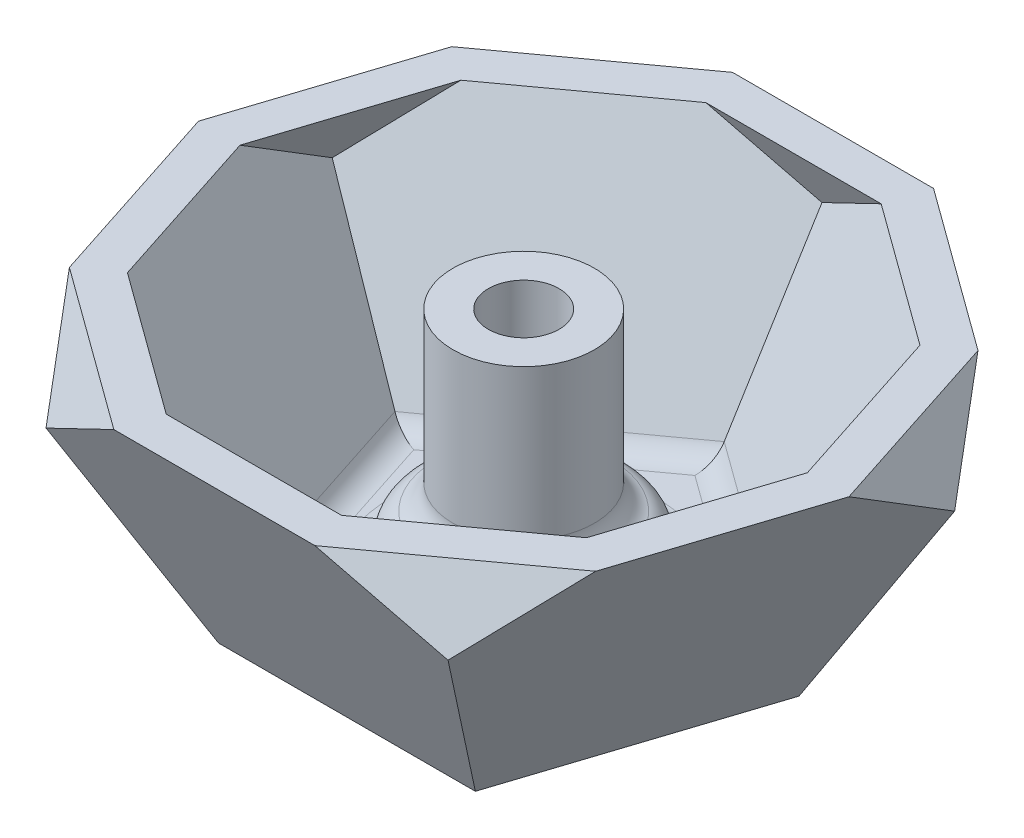
SolidWorks part; units mm, degrees
ref_plane "Front Plane" through (0, 0, 0) normal (0, 0, 1) x (1, 0, 0)
ref_plane "Top Plane" through (0, 0, 0) normal (0, 1, 0) x (1, 0, 0)
ref_plane "Right Plane" through (0, 0, 0) normal (1, 0, 0) x (0, 0, -1)
sketch "Sketch1" plane through (0, 0, 0) normal (0, 1, 0) x (1, 0, 0)
  line L1 (0, 12.3607) -> (-11.7557, 3.8197)
  line L2 (-11.7557, 3.8197) -> (-7.2654, -10)
  line L3 (-7.2654, -10) -> (7.2654, -10)
  line L4 (7.2654, -10) -> (11.7557, 3.8197)
  line L5 (11.7557, 3.8197) -> (0, 12.3607)
  circle A0 centre (0, 0) radius 10 construction
  dimension "D1" = 20
extrude "Boss-Extrude1" add sketch "Sketch1" along normal blind 30 draft 26.565 draft outward yes
sketch "Sketch3" plane through (0, 30, 0) normal (0, 1, 0) x (1, 0, 0)
  line L0 (0, 0) -> (14.6946, 20.2254) construction
  line L1 (7.2654, 10) -> (-7.2654, 10)
  line L2 (-7.2654, 10) -> (-11.7557, -3.8197)
  line L3 (-11.7557, -3.8197) -> (0, -12.3607)
  line L4 (0, -12.3607) -> (11.7557, -3.8197)
  line L5 (11.7557, -3.8197) -> (7.2654, 10)
  line L6 (29.3893, 9.5492) -> (0, 30.9017) construction
  circle A0 centre (0, 0) radius 10 construction
  dimension "D1" = 20
extrude "Cut-Extrude1" cut sketch "Sketch3" against normal blind 30 draft 26.565 flip side to cut
sketch "Sketch4" plane through (0, 0, 0) normal (1, 0, 0) x (0, 0, -1)
  line L0 (-3.8197, 30) -> (-3.8197, 0) construction
  line L1 (-10, 0) -> (3.8197, 0) construction
  point P5 (-3.8197, 15)
ref_plane "Plane1" through (0, 15, 0) normal (0, 1, 0) x (1, 0, 0)
sketch "Sketch5" plane through (0, 15, 0) normal (0, 1, 0) x (1, 0, 0)
  circle A0 centre (0, 0) radius 19.3475
extrude "Cut-Extrude2" cut sketch "Sketch5" along normal blind 25
shell "Shell1" thickness 2 removed face at (0, 15, 0)
sketch "Sketch6" plane through (0, 2, 0) normal (0, 1, 0) x (1, 0, 0)
  circle A0 centre (0, 0) radius 4
  circle A1 centre (0, 0) radius 2
  dimension "D1" = 8
  dimension "D2" = 4
extrude "Boss-Extrude2" add sketch "Sketch6" along direction (0, 1, 0) on the side of the normal up to surface (13 mm away) up to face at (0, 15, 0)
sketch "Sketch10" plane through (0, 2, 0) normal (0, 1, 0) x (1, 0, 0)
  circle A5 centre (0, 0) radius 4 construction
  circle A6 centre (0, 0) radius 4
  circle A7 centre (0, 0) radius 6
  circle A8 centre (0, 0) radius 4.5
  circle M18 centre (0, 0) radius 4
  dimension "D1" = 12
  dimension "D2" = 9
extrude "Boss-Extrude4" add sketch "Sketch10" along normal blind 3 contours A7 A8 | A8 M18 region at (-5.8303, 2, 0) region at (-4.3727, 2, 0)
fillet "Fillet5" radius 1.5 7 edges at (5.1513, 2, -7.0902) (8.335, 2, 2.7082) (0, 2, 8.7639) (-8.335, 2, 2.7082) (-5.1513, 2, -7.0902) (0, 2, 6) (0, 5, 4)
extrude "Cut-Extrude3" cut sketch "Sketch10<3>" against normal up to surface (2 mm away) and the other way blind 2 contours M18 | A8 M18 region at (0, 2, 0) region at (-4.3727, 2, 0) up to face at (0, 0, 0)
sketch "Sketch10<3>" plane through (0, 2, 0) normal (0, 1, 0) x (1, 0, 0) same geometry as "Sketch10"
fillet "Fillet6" radius 1.5 2 edges at (0, 4, 4.5) (0, 5, 6)
